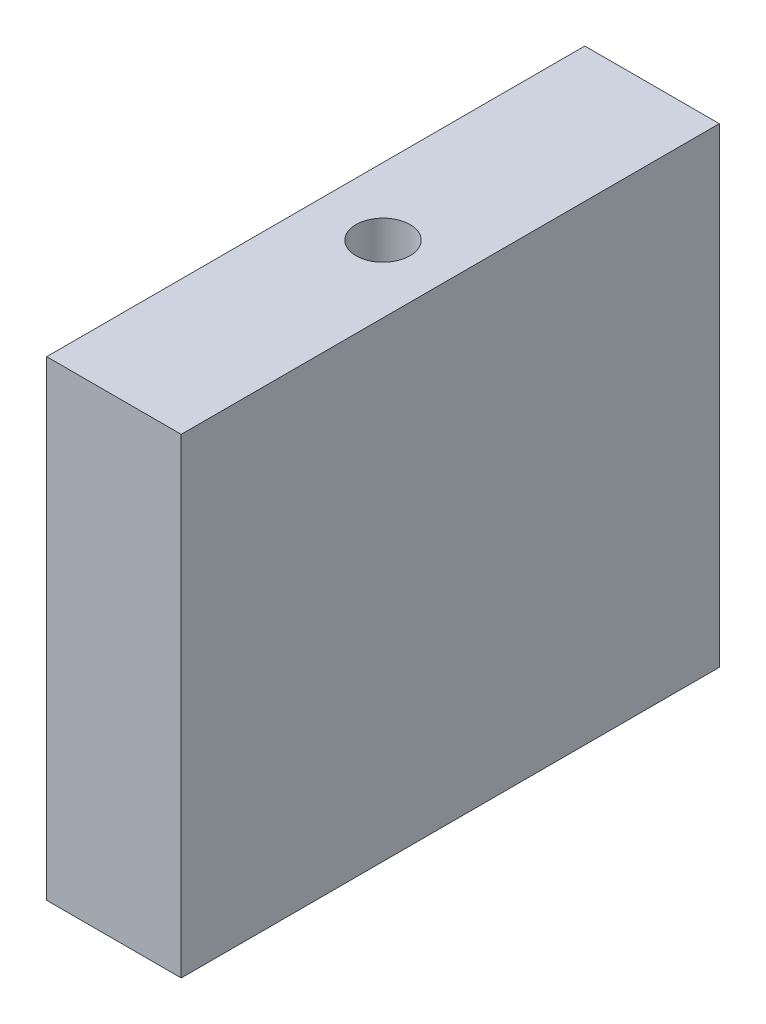
SolidWorks part; units mm, degrees
note: '?' marks a value the reader was unsure of.
material "ALUMINUM 6061"
ref_plane "Front" through (0, 0, 0) normal (0, 0, 1) x (1, 0, 0)
ref_plane "Top" through (0, 0, 0) normal (0, 1, 0) x (1, 0, 0)
ref_plane "Right" through (0, 0, 0) normal (1, 0, 0) x (0, 0, -1)
ref_axis "Axis1" through (0, 50, 0) along (0, -1, 0)?
sketch "Sketch1" plane through (0, 0, 0) normal (1, 0, 0) x (0, 0, -1)
  line L1 (-34.925, 25.4) -> (15.875, 25.4)
  line L2 (-34.925, 25.4) -> (-34.925, -19.05)
  line L3 (-34.925, -19.05) -> (15.875, -19.05)
  line L4 (15.875, 25.4) -> (15.875, -19.05)
  dimension "D1" = 50.8
  dimension "D2" = 44.45
  dimension "D3" = 25.4
  dimension "D4" = 34.925
extrude "Extrude1" add sketch "Sketch1" along normal mid plane 12.7
sketch "Sketch2" plane through (6.35, 0, 0) normal (1, 0, 0) x (0, 0, -1)
  circle A0 centre (0, 0) radius 4.7752
  dimension "D1" = 9.5504
extrude "Extrude2" [suppressed] cut sketch "Sketch2" against normal through all
hole_wizard "1/4-20 Tapped Hole1" positions "Sketch4" profile "Sketch3" tap size "1/4-20" standard "Ansi Inch"
sketch "Sketch4" plane through (0, -19.05, 0) normal (0, -1, 0) x (1, 0, 0)
  line L0 (6.35, 34.925) -> (-6.35, 34.925) construction
  point P0 (0, 26.035)
  point P1 (0, -5.715)
  dimension "D1" = 31.75
  dimension "D2" = 8.89
cosmetic thread "Hole Thread1"
cosmetic thread "Hole Thread2"
sketch "Sketch3" plane through (0, -19.05, 26.035) normal (1, 0, 0) x (0, 0, -1)
  line L0 (0, 0) -> (0, 16.4436)
  line L1 (0, 16.4436) -> (2.5527, 14.9098)
  line L2 (2.5527, 14.9098) -> (2.5527, 1.8554)
  line L3 (2.5527, 1.8554) -> (4.1656, 0)
  line L5 (4.1656, 0) -> (0, 0)
  line L6 (-2.5527, 1.8554) -> (-4.1656, 0) construction
  line L10 (0, 16.4436) -> (-2.5527, 14.9098) construction
  line L11 (0, -6.35) -> (0, 107.95) construction
  dimension "Tap Drill Dia." = 5.1054
  dimension "Tap Drill Depth" = 14.9098
  dimension "Near C'Sink Dia." = 8.3312
  dimension "Near C'Sink Angle" = 82
  dimension "Drill Angle" = 118
hole_wizard "1/4-20 Tapped Hole2" positions "Sketch6" profile "Sketch5" tap size "1/4-20" standard "Ansi Inch"
sketch "Sketch6" plane through (0, 25.4, 0) normal (0, 1, 0) x (-1, 0, 0)
  line L0 (-6.35, 34.925) -> (6.35, 34.925) construction
  point P0 (0, 9.525)
  dimension "D1" = 25.4
sketch "Sketch5" plane through (0, 25.4, 9.525) normal (1, 0, 0) x (0, 0, 1)
  line L0 (0, 0) -> (0, 18.0438)
  line L1 (0, 18.0438) -> (2.5527, 16.51)
  line L2 (2.5527, 16.51) -> (2.5527, 0)
  line L5 (2.5527, 0) -> (0, 0)
  line L10 (0, 18.0438) -> (-2.5527, 16.51) construction
  line L11 (0, -6.35) -> (0, 107.95) construction
  dimension "Tap Drill Dia." = 5.1054
  dimension "Tap Drill Depth" = 16.51
  dimension "Drill Angle" = 118
cosmetic thread "Hole Thread3"
hole_wizard "#10-24 Tapped Hole1" [suppressed] positions "Sketch8" profile "Sketch7" tap size "#10-24" standard "Ansi Inch"
sketch "Sketch8" plane through (0, 0, -15.875) normal (0, 0, -1) x (-1, 0, 0)
  point P0 (0, 0)
sketch "Sketch7" plane through (0, 0, -15.875) normal (1, 0, 0) x (0, 1, 0)
  line L0 (0, 0) -> (0, 50.8)
  line L1 (0, 50.8) -> (1.8986, 50.8)
  line L2 (1.8986, 50.8) -> (1.8986, 0)
  line L5 (1.8986, 0) -> (0, 0)
  line L11 (0, -6.35) -> (0, 107.95) construction
  dimension "Thru Tap Drill Dia." = 3.7973
  dimension "Thru Tap Drill Depth" = 50.8
cosmetic thread "Hole Thread4" [suppressed] parameters "D2"=4.826
